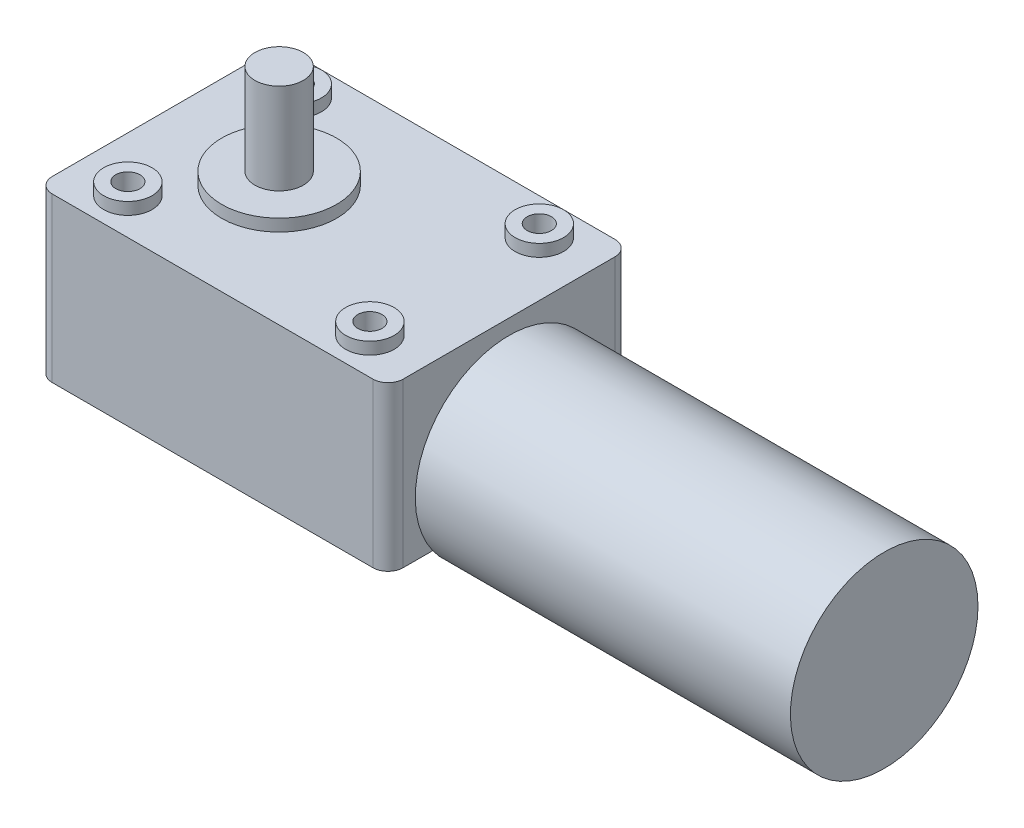
SolidWorks part; units mm, degrees
ref_plane "Front Plane" through (0, 0, 0) normal (0, 0, 1) x (1, 0, 0)
ref_plane "Top Plane" through (0, 0, 0) normal (0, 1, 0) x (1, 0, 0)
ref_plane "Right Plane" through (0, 0, 0) normal (1, 0, 0) x (0, 0, -1)
sketch "Sketch1" plane through (0, 0, 0) normal (0, 1, 0) x (1, 0, 0)
  line L1 (-26.5, -20) -> (26.5, -20)
  line L2 (-29, -17.5) -> (-29, 17.5)
  line L3 (-26.5, 20) -> (26.5, 20)
  line L4 (29, -17.5) -> (29, 17.5)
  line L5 (-29, -20) -> (29, 20) construction
  line L6 (-29, 20) -> (29, -20) construction
  arc A0 (-29, -17.5) -> (-26.5, -20) centre (-26.5, -17.5) ccw
  arc A1 (26.5, -20) -> (29, -17.5) centre (26.5, -17.5) ccw
  arc A2 (29, 17.5) -> (26.5, 20) centre (26.5, 17.5) ccw
  arc A3 (-29, 17.5) -> (-26.5, 20) centre (-26.5, 17.5) cw
  point P0 (0, 0)
  dimension "D3" = 2.5
  dimension "D1" = 58
  dimension "D2" = 40
extrude "Boss-Extrude1" add sketch "Sketch1" along normal mid plane 27
sketch "Sketch2" plane through (0, 13.5, 0) normal (0, 1, 0) x (1, 0, 0)
  line L0 (-1000, 0) -> (49000, 0) construction
  line L1 (-1000.4558, 14) -> (48999.5442, 14) construction
  line L2 (-1000.9116, -14) -> (48999.0884, -14) construction
  line L3 (-20, -994.0746) -> (-20, 49005.9254) construction
  line L4 (20, -995.2141) -> (20, 49004.7859) construction
  line L5 (-29, 17.5) -> (-29, -17.5) construction
  circle A0 centre (-20, 14) radius 4
  circle A1 centre (-20, -14) radius 4
  circle A2 centre (20, -14) radius 4
  circle A3 centre (20, 14) radius 4
  circle A4 centre (-9, 0) radius 9.5
  dimension "D5" = 8
  dimension "D6" = 8
  dimension "D7" = 8
  dimension "D8" = 8
  dimension "D9" = 19
  dimension "D1" = 14
  dimension "D2" = 14
  dimension "D3" = 9
  dimension "D4" = 40
  dimension "D10" = 20
extrude "Boss-Extrude2" add sketch "Sketch2" along normal blind 2
sketch "Sketch3" plane through (0, 15.5, 0) normal (0, 1, 0) x (1, 0, 0)
  circle A0 centre (-20, 14) radius 2
  circle A1 centre (20, 14) radius 2
  circle A2 centre (20, -14) radius 2
  circle A3 centre (-20, -14) radius 2
  dimension "D1" = 4
  dimension "D2" = 4
  dimension "D3" = 4
  dimension "D4" = 4
extrude "Cut-Extrude1" cut sketch "Sketch3" against normal blind 6
sketch "Sketch4" plane through (0, 15.5, 0) normal (0, 1, 0) x (1, 0, 0)
  circle A0 centre (-9, 0) radius 4
  dimension "D1" = 8
extrude "Boss-Extrude3" add sketch "Sketch4" along normal blind 15
sketch "Sketch5" plane through (29, 0, 0) normal (1, 0, 0) x (0, 0, -1)
  line L0 (-17.5, 13.5) -> (17.5, 13.5) construction
  line L1 (0, -1000) -> (0, 49000) construction
  circle A0 centre (0, -4.5) radius 15.5
  dimension "D2" = 31
  dimension "D3" = 18
extrude "Boss-Extrude4" add sketch "Sketch5" along normal blind 62
